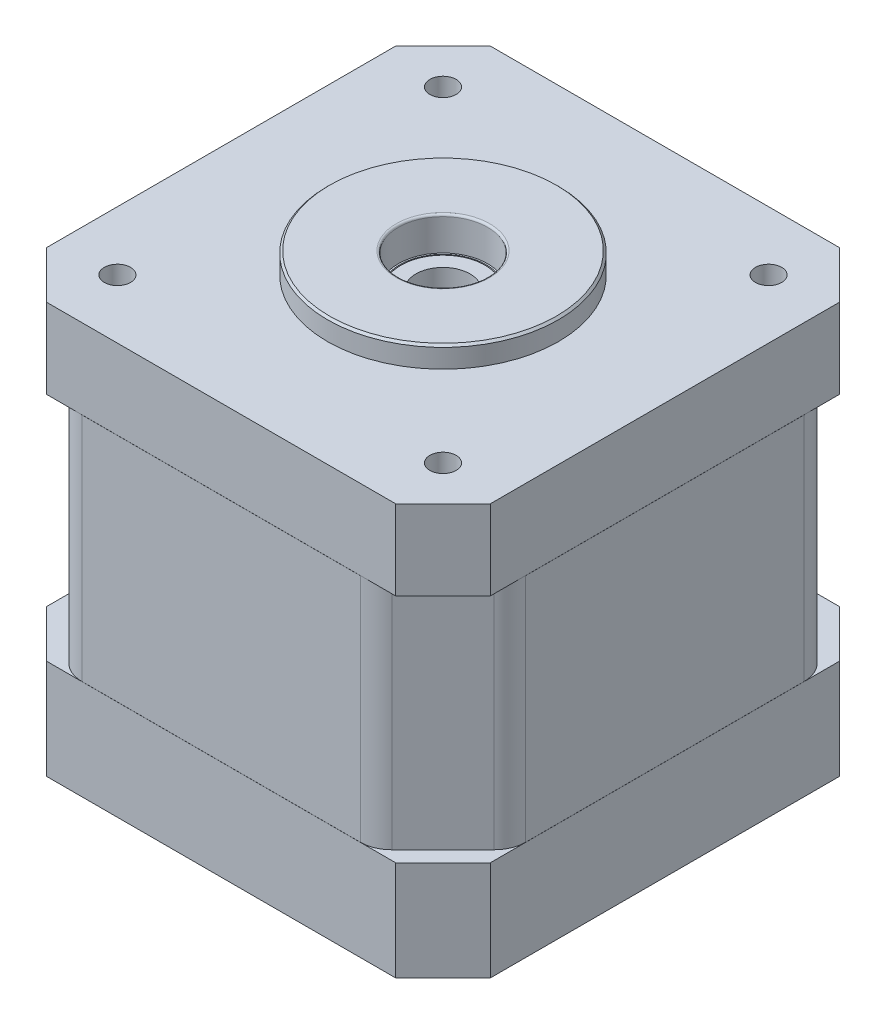
SolidWorks part; units mm, degrees
other "Cámara1"
material "Acero al carbono fundido"
ref_plane "Alzado" through (0, 0, 0) normal (0, 0, 1) x (1, 0, 0)
ref_plane "Planta" through (0, 0, 0) normal (0, 1, 0) x (1, 0, 0)
ref_plane "Vista lateral" through (0, 0, 0) normal (1, 0, 0) x (0, 0, -1)
sketch "Croquis1" plane through (0, 0, 0) normal (0, 1, 0) x (1, 0, 0)
  line L0 (-21.125, 16.625) -> (-16.625, 21.125)
  line L1 (-16.625, -21.125) -> (16.625, -21.125)
  line L2 (-21.125, -16.625) -> (-21.125, 16.625)
  line L3 (-16.625, 21.125) -> (16.625, 21.125)
  line L4 (21.125, -16.625) -> (21.125, 16.625)
  line L5 (-21.125, -21.125) -> (21.125, 21.125) construction
  line L6 (-21.125, 21.125) -> (21.125, -21.125) construction
  line L7 (16.625, 21.125) -> (21.125, 16.625)
  line L8 (-21.125, -16.625) -> (-16.625, -21.125)
  line L9 (16.625, -21.125) -> (21.125, -16.625)
  circle A0 centre (-15.5, 15.5) radius 1
  circle A1 centre (15.5, 15.5) radius 1
  circle A2 centre (-15.5, -15.5) radius 1
  circle A3 centre (15.5, -15.5) radius 1
  point P0 (0, 0)
  dimension "D3" = 2
  dimension "D4" = 31
  dimension "D5" = 31
  dimension "D1" = 42.25
  dimension "D2" = 42.25
extrude "Saliente-Extruir1" add sketch "Croquis1" along normal blind 7.6
sketch "Croquis2" plane through (0, 7.6, 0) normal (0, 1, 0) x (1, 0, 0)
  circle A0 centre (0, 0) radius 11
  dimension "D1" = 22
extrude "Saliente-Extruir2" add sketch "Croquis2" along normal blind 2
chamfer "Chaflán1" distance 0.2 angle 45 1 edges at (0, 9.6, 11)
sketch "Croquis3" plane through (0, 9.6, 0) normal (0, 1, 0) x (1, 0, 0)
  circle A0 centre (0, 0) radius 4.25
  dimension "D1" = 8.5
extrude "Cortar-Extruir1" cut sketch "Croquis3" against normal blind 3.2
fillet "Redondeo1" radius 0.2 1 edges at (0, 9.6, 4.25)
sketch "Croquis4" plane through (0, 6.4, 0) normal (0, 1, 0) x (1, 0, 0)
  circle A0 centre (0, 0) radius 4.1
  circle A1 centre (0, 0) radius 4
  dimension "D1" = 8.2
  dimension "D2" = 8
extrude "Cortar-Extruir2" cut sketch "Croquis4" against normal blind 0.5
sketch "Croquis5" plane through (0, 6.4, 0) normal (0, 1, 0) x (1, 0, 0)
  circle A0 centre (0, 0) radius 2.5
  dimension "D1" = 5
extrude "Saliente-Extruir3" add sketch "Croquis5" along normal blind 21.2
chamfer "Chaflán2" distance 0.3 angle 45 1 edges at (0, 27.6, 2.5)
sketch "Croquis7" plane through (0, 27.6, 0) normal (0, 1, 0) x (1, 0, 0)
  line L0 (0, -2.5) -> (0, 2) construction
  line L1 (-1.5, 2) -> (1.5, 2)
  circle A0 centre (0, 0) radius 2.5 construction
  circle A1 centre (0, 0) radius 2.5 construction
  arc A2 (1.5, 2) -> (-1.5, 2) centre (0, 0) ccw
  point P11 (0, 2)
  dimension "D1" = 4.5
extrude "Cortar-Extruir4" cut sketch "Croquis7" against normal blind 17.2
fillet "Redondeo2" radius 0.1 1 edges at (0, 10.4, -2)
chamfer "Chaflán3" distance 0.3 angle 45 1 edges at (0, 27.6, -2)
sketch "Croquis8" plane through (0, 0, 0) normal (0, -1, 0) x (1, 0, 0)
  line L0 (-14.5, 21.125) -> (14.5, 21.125)
  line L1 (-16.625, 21.125) -> (16.625, 21.125) construction
  line L2 (0, 21.125) -> (0, 0) construction
  line L3 (0, 0) -> (-21.125, 0) construction
  line L4 (-21.125, -16.625) -> (-21.125, 16.625) construction
  line L5 (-21.125, -14.5) -> (-21.125, 14.5)
  line L6 (-21.125, 14.5) -> (-14.5, 21.125)
  line L7 (21.125, -14.5) -> (21.125, 14.5)
  line L8 (-14.5, -21.125) -> (14.5, -21.125)
  line L9 (-21.125, -14.5) -> (-14.5, -21.125)
  line L10 (14.5, -21.125) -> (21.125, -14.5)
  line L11 (21.125, 14.5) -> (14.5, 21.125)
  point P5 (0, 21.125)
  point P14 (-21.125, 0)
  dimension "D1" = 29
  dimension "D2" = 29
extrude "Saliente-Extruir4" add sketch "Croquis8" along normal blind 22
sketch "Croquis9" plane through (0, -22, 0) normal (0, -1, 0) x (1, 0, 0)
  line L8 (16.625, 21.125) -> (-16.625, 21.125)
  line L9 (21.125, 16.625) -> (16.625, 21.125)
  line L10 (21.125, -16.625) -> (21.125, 16.625)
  line L11 (16.625, -21.125) -> (21.125, -16.625)
  line L12 (-16.625, -21.125) -> (16.625, -21.125)
  line L13 (-21.125, -16.625) -> (-16.625, -21.125)
  line L14 (-21.125, 16.625) -> (-21.125, -16.625)
  line L15 (-16.625, 21.125) -> (-21.125, 16.625)
  line L16 (16.625, 21.125) -> (-16.625, 21.125)
  line L17 (21.125, 16.625) -> (16.625, 21.125)
  line L18 (21.125, -16.625) -> (21.125, 16.625)
  line L19 (16.625, -21.125) -> (21.125, -16.625)
  line L20 (-16.625, -21.125) -> (16.625, -21.125)
  line L21 (-21.125, -16.625) -> (-16.625, -21.125)
  line L22 (-21.125, 16.625) -> (-21.125, -16.625)
  line L23 (-16.625, 21.125) -> (-21.125, 16.625)
  dimension "D5" = 0
extrude "Saliente-Extruir5" add sketch "Croquis9" along normal blind 9.5
sketch "Croquis10" plane through (0, -31.5, 0) normal (0, -1, 0) x (1, 0, 0)
  line L0 (-8.175, -21.125) -> (8.175, -21.125)
  line L1 (-16.625, -21.125) -> (16.625, -21.125) construction
  line L2 (0, 0) -> (0, -21.125) construction
  line L3 (8.175, -21.125) -> (8.175, -25.125)
  line L4 (8.175, -25.125) -> (-8.175, -25.125)
  line L5 (-8.175, -25.125) -> (-8.175, -21.125)
  point P5 (0, -21.125)
  dimension "D1" = 16.35
  dimension "D2" = 4
extrude "Saliente-Extruir6" add sketch "Croquis10" against normal blind 3.3
sketch "Croquis11" plane through (0, 6.4, 0) normal (0, 1, 0) x (1, 0, 0)
  circle A0 centre (0, 0) radius 2.575
  circle A1 centre (0, 0) radius 2.5 construction
  circle A2 centre (0, 0) radius 2.5
  arc A3 (-1.5, 2) -> (1.5, 2) centre (0, 0) ccw construction
  dimension "D1" = 5.15
extrude "Cortar-Extruir5" cut sketch "Croquis11" against normal up to surface (0.5 mm away) up to face at (0, 5.9, 4)
sketch "Croquis12" plane through (0, -28.2, 0) normal (0, 1, 0) x (1, 0, 0)
  line L0 (-7, 21.125) -> (7, 21.125)
  line L1 (16.625, 21.125) -> (-16.625, 21.125) construction
  line L2 (-7, 21.125) -> (-7, 25.825)
  line L3 (-7, 25.825) -> (7, 25.825)
  line L4 (7, 25.825) -> (7, 21.125)
  point P5 (0, 21.125)
  dimension "D1" = 14
  dimension "D2" = 4.7
extrude "Saliente-Extruir7" add sketch "Croquis12" along normal blind 1
sketch "Croquis13" plane through (0, -27.2, 0) normal (0, 1, 0) x (1, 0, 0)
  line L0 (16.625, 21.125) -> (-16.625, 21.125) construction
  line L1 (-7.6, 21.125) -> (7.6, 21.125)
  line L2 (7.6, 21.125) -> (7.6, 27.625)
  line L3 (7.6, 27.625) -> (-7.6, 27.625)
  line L4 (-7.6, 27.625) -> (-7.6, 21.125)
  point P0 (0, 21.125)
  point P6 (0, 21.125)
  dimension "D1" = 15.2
  dimension "D2" = 6.5
extrude "Saliente-Extruir8" add sketch "Croquis13" along normal blind 5.5
sketch "Croquis14" plane through (0, 0, -27.625) normal (0, 0, -1) x (-1, 0, 0)
  line L4 (0, -22.7) -> (0, -21.7) construction
  line L5 (7.6, -21.7) -> (-7.6, -21.7) construction
  line L6 (4, -22.7) -> (4, -21.7)
  line L7 (-4, -22.7) -> (-4, -21.7)
  line L8 (-6.6, -26.2) -> (6.6, -26.2)
  line L9 (6.6, -26.2) -> (6.6, -22.7)
  line L10 (6.6, -22.7) -> (-6.6, -22.7)
  line L11 (-6.6, -22.7) -> (-6.6, -26.2)
  line L12 (-6.6, -26.2) -> (6.6, -26.2)
  line L13 (6.6, -26.2) -> (6.6, -22.7)
  line L14 (6.6, -22.7) -> (4, -22.7)
  line L15 (-6.6, -22.7) -> (-6.6, -26.2)
  line L16 (-7.6, -21.7) -> (7.6, -21.7) construction
  line L20 (-4, -21.7) -> (4, -21.7)
  line L21 (-4, -22.7) -> (-6.6, -22.7)
  point P1 (0, -22.7)
  dimension "D2" = 4
  dimension "D1" = 1
  dimension "D3" = 4
extrude "Cortar-Extruir6" cut sketch "Croquis14" against normal blind 4.1
sketch "Croquis15" plane through (0, 0, -23.525) normal (0, 0, -1) x (-1, 0, 0)
  line L0 (-6.6, -24.45) -> (6.6, -24.45) construction
  line L1 (-6.6, -22.7) -> (-6.6, -26.2) construction
  line L2 (6.6, -26.2) -> (6.6, -22.7) construction
  line L3 (-3.0743, -24.2) -> (-2.5743, -24.2)
  line L4 (-4.9643, -24.7) -> (-4.4643, -24.7)
  line L5 (-4.9643, -24.7) -> (-4.9643, -24.2)
  line L6 (-4.9643, -24.2) -> (-4.4643, -24.2)
  line L7 (-4.4643, -24.7) -> (-4.4643, -24.2)
  line L8 (-4.9643, -24.7) -> (-4.4643, -24.2) construction
  line L9 (-4.9643, -24.2) -> (-4.4643, -24.7) construction
  line L10 (-2.5743, -24.7) -> (-2.5743, -24.2)
  line L11 (-3.0743, -24.7) -> (-2.5743, -24.7)
  line L12 (-3.0743, -24.7) -> (-3.0743, -24.2)
  line L13 (-1.1843, -24.2) -> (-0.6843, -24.2)
  line L14 (-0.6843, -24.7) -> (-0.6843, -24.2)
  line L15 (-1.1843, -24.7) -> (-0.6843, -24.7)
  line L16 (-1.1843, -24.7) -> (-1.1843, -24.2)
  line L17 (0.7057, -24.2) -> (1.2057, -24.2)
  line L18 (1.2057, -24.7) -> (1.2057, -24.2)
  line L19 (0.7057, -24.7) -> (1.2057, -24.7)
  line L20 (0.7057, -24.7) -> (0.7057, -24.2)
  line L21 (2.5957, -24.2) -> (3.0957, -24.2)
  line L22 (3.0957, -24.7) -> (3.0957, -24.2)
  line L23 (2.5957, -24.7) -> (3.0957, -24.7)
  line L24 (2.5957, -24.7) -> (2.5957, -24.2)
  line L25 (4.4857, -24.2) -> (4.9857, -24.2)
  line L26 (4.9857, -24.7) -> (4.9857, -24.2)
  line L27 (4.4857, -24.7) -> (4.9857, -24.7)
  line L28 (4.4857, -24.7) -> (4.4857, -24.2)
  point P6 (-4.7143, -24.45)
  dimension "D1" = 0.5
  dimension "D2" = 13.2
  dimension "D3" = 1.8857
  dimension "D4" = 6
extrude "Saliente-Extruir9" add sketch "Croquis15" along normal blind 3.5
chamfer "Chaflán4" distance 0.25 angle 45 24 edges at (-2.8457, -24.7, -27.025) (-2.5957, -24.45, -27.025) (-2.8457, -24.2, -27.025) (-3.0957, -24.45, -27.025) (-4.7357, -24.7, -27.025) (-4.4857, -24.45, -27.025) (-4.7357, -24.2, -27.025) (-4.9857, -24.45, -27.025) (2.8243, -24.7, -27.025) (3.0743, -24.45, -27.025) (2.8243, -24.2, -27.025) (2.5743, -24.45, -27.025) (0.9343, -24.7, -27.025) (1.1843, -24.45, -27.025) (0.9343, -24.2, -27.025) (0.6843, -24.45, -27.025) (-0.9557, -24.7, -27.025) (-0.7057, -24.45, -27.025) (-0.9557, -24.2, -27.025) (-1.2057, -24.45, -27.025) (4.7143, -24.7, -27.025) (4.9643, -24.45, -27.025) (4.7143, -24.2, -27.025) (4.4643, -24.45, -27.025)
sketch "Croquis16" plane through (0, -31.5, 0) normal (0, -1, 0) x (1, 0, 0)
  circle A0 centre (-15.5, 15.5) radius 3
  circle A1 centre (15.5, 15.5) radius 1
  circle A2 centre (15.5, 15.5) radius 1 construction
  circle A3 centre (-15.5, 15.5) radius 1
  circle A4 centre (-15.5, 15.5) radius 1 construction
  circle A5 centre (15.5, -15.5) radius 1
  circle A6 centre (15.5, -15.5) radius 1 construction
  circle A7 centre (-15.5, -15.5) radius 1
  circle A8 centre (-15.5, -15.5) radius 1 construction
  circle A9 centre (15.5, 15.5) radius 3
  circle A10 centre (-15.5, -15.5) radius 3
  circle A11 centre (15.5, -15.5) radius 3
  dimension "D6" = 6
  dimension "D1" = 0
  dimension "D2" = 0
  dimension "D3" = 0
  dimension "D4" = 0
extrude "Cortar-Extruir7" cut sketch "Croquis16" against normal blind 2.5
sketch "Croquis17" plane through (0, -29, 0) normal (0, -1, 0) x (1, 0, 0)
  circle A0 centre (15.5, 15.5) radius 2.75
  circle A1 centre (-15.5, 15.5) radius 2.75
  circle A2 centre (15.5, -15.5) radius 2.75
  circle A3 centre (-15.5, -15.5) radius 2.75
  dimension "D1" = 5.5
  dimension "D2" = 5.5
  dimension "D3" = 5.5
  dimension "D4" = 5.5
extrude "Saliente-Extruir10" add sketch "Croquis17" along normal blind 2.3
fillet "Redondeo3" radius 0.6 4 edges at (15.5, -31.3, -18.25) (-15.5, -31.3, -18.25) (-15.5, -31.3, 12.75) (15.5, -31.3, 12.75)
sketch "Croquis18" plane through (0, -31.3, 0) normal (0, -1, 0) x (1, 0, 0)
  line L0 (16.8789, 14.1211) -> (14.1211, 16.8789) construction
  line L1 (15.5, 15.5) -> (15.5, 17.65) construction
  line L2 (17.3031, 14.5454) -> (16.3485, 15.5)
  line L3 (16.4546, 13.6969) -> (15.5, 14.6515)
  line L4 (14.1211, 14.1211) -> (16.8789, 16.8789) construction
  line L5 (14.5454, 13.6969) -> (15.5, 14.6515)
  line L6 (13.6969, 14.5454) -> (14.6515, 15.5)
  line L7 (16.4546, 17.3031) -> (17.3031, 16.4546)
  line L8 (17.3031, 14.5454) -> (16.4546, 13.6969)
  line L9 (14.5454, 13.6969) -> (13.6969, 14.5454)
  line L10 (13.6969, 16.4546) -> (14.5454, 17.3031)
  line L11 (15.5, 16.3485) -> (14.5454, 17.3031)
  line L12 (16.3485, 15.5) -> (17.3031, 16.4546)
  line L13 (17.3031, 14.5454) -> (14.5454, 17.3031) construction
  line L14 (14.6515, 15.5) -> (13.6969, 16.4546)
  line L15 (14.5454, 13.6969) -> (17.3031, 16.4546) construction
  line L16 (15.5, 16.3485) -> (16.4546, 17.3031)
  line L17 (16.4546, 13.6969) -> (13.6969, 16.4546) construction
  line L18 (-17.3031, 16.4546) -> (-16.4546, 17.3031)
  line L19 (13.6969, 14.5454) -> (16.4546, 17.3031) construction
  line L20 (-15.5, 16.3485) -> (-14.5454, 17.3031)
  line L21 (-14.5454, 13.6969) -> (-15.5, 14.6515)
  line L22 (-16.3485, 15.5) -> (-17.3031, 16.4546)
  line L23 (-13.6969, 14.5454) -> (-14.5454, 13.6969)
  line L24 (-16.4546, 13.6969) -> (-15.5, 14.6515)
  line L25 (-14.5454, 17.3031) -> (-13.6969, 16.4546)
  line L26 (-15.5, 15.5) -> (-15.5, 17.65) construction
  line L27 (-15.5, 16.3485) -> (-16.4546, 17.3031)
  line L28 (-13.6969, 14.5454) -> (-14.6515, 15.5)
  line L29 (-16.4546, 13.6969) -> (-17.3031, 14.5454)
  line L30 (-17.3031, 14.5454) -> (-16.3485, 15.5)
  line L31 (-16.8789, 14.1211) -> (-14.1211, 16.8789) construction
  line L32 (-14.6515, 15.5) -> (-13.6969, 16.4546)
  line L33 (-14.1211, 14.1211) -> (-16.8789, 16.8789) construction
  line L34 (-13.6969, -16.4546) -> (-14.6515, -15.5)
  line L35 (-14.6515, -15.5) -> (-13.6969, -14.5454)
  line L36 (-15.5, -14.6515) -> (-16.4546, -13.6969)
  line L37 (-14.5454, -17.3031) -> (-15.5, -16.3485)
  line L38 (-17.3031, -16.4546) -> (-16.3485, -15.5)
  line L39 (-13.6969, -16.4546) -> (-14.5454, -17.3031)
  line L40 (-15.5, -14.6515) -> (-14.5454, -13.6969)
  line L41 (-16.4546, -17.3031) -> (-15.5, -16.3485)
  line L42 (-16.3485, -15.5) -> (-17.3031, -14.5454)
  line L43 (-16.4546, -17.3031) -> (-17.3031, -16.4546)
  line L44 (-14.1211, -16.8789) -> (-16.8789, -14.1211) construction
  line L45 (-14.5454, -13.6969) -> (-13.6969, -14.5454)
  line L46 (-16.8789, -16.8789) -> (-14.1211, -14.1211) construction
  line L47 (-15.5, -15.5) -> (-15.5, -13.35) construction
  line L48 (-17.3031, -14.5454) -> (-16.4546, -13.6969)
  line L49 (16.3485, -15.5) -> (17.3031, -14.5454)
  line L50 (13.6969, -16.4546) -> (14.6515, -15.5)
  line L51 (16.8789, -16.8789) -> (14.1211, -14.1211) construction
  line L52 (17.3031, -16.4546) -> (16.4546, -17.3031)
  line L53 (14.6515, -15.5) -> (13.6969, -14.5454)
  line L54 (14.5454, -17.3031) -> (15.5, -16.3485)
  line L55 (14.1211, -16.8789) -> (16.8789, -14.1211) construction
  line L56 (15.5, -15.5) -> (15.5, -13.35) construction
  line L57 (14.5454, -17.3031) -> (13.6969, -16.4546)
  line L58 (16.4546, -13.6969) -> (17.3031, -14.5454)
  line L59 (17.3031, -16.4546) -> (16.3485, -15.5)
  line L60 (16.4546, -17.3031) -> (15.5, -16.3485)
  line L61 (15.5, -14.6515) -> (16.4546, -13.6969)
  line L62 (13.6969, -14.5454) -> (14.5454, -13.6969)
  line L63 (15.5, -14.6515) -> (14.5454, -13.6969)
  circle A0 centre (15.5, 15.5) radius 2.15 construction
  point P4 (15.5, 15.5)
  point P8 (15.5, 15.5)
  point P16 (15.5, 15.5)
  point P28 (-15.5, 15.5)
  point P30 (-15.5, 15.5)
  point P37 (-15.5, 15.5)
  point P49 (-15.5, -15.5)
  point P51 (-15.5, -15.5)
  point P58 (-15.5, -15.5)
  point P70 (15.5, -15.5)
  point P72 (15.5, -15.5)
  point P79 (15.5, -15.5)
  dimension "D1" = 3.9
  dimension "D2" = 45
  dimension "D5" = 3.9
  dimension "D6" = 45
  dimension "D9" = 45
  dimension "D8" = 3.9
  dimension "D10" = 3.9
  dimension "D11" = 45
  dimension "D12" = 3.9
  dimension "D13" = 45
  dimension "D14" = 3.9
  dimension "D15" = 45
  dimension "D3" = 0.6
  dimension "D4" = 0.6
  dimension "D7" = 0.6
extrude "Cortar-Extruir8" cut sketch "Croquis18" against normal blind 1.1 draft 10
fillet "Redondeo4" radius 0.2 48 edges at (-17.166, -30.75, -14.5454) (-16.2114, -30.75, -15.5) (-17.166, -30.75, -16.4546) (-16.4546, -30.75, -17.166) (-15.5, -30.75, -16.2114) (-14.5454, -30.75, -17.166) (-13.834, -30.75, -16.4546) (-14.7886, -30.75, -15.5) (-13.834, -30.75, -14.5454) (-14.5454, -30.75, -13.834) (-15.5, -30.75, -14.7886) (-16.4546, -30.75, -13.834) (13.834, -30.75, -14.5454) (14.7886, -30.75, -15.5) (13.834, -30.75, -16.4546) (14.5454, -30.75, -17.166) (15.5, -30.75, -16.2114) (16.4546, -30.75, -17.166) (17.166, -30.75, -16.4546) (16.2114, -30.75, -15.5) (17.166, -30.75, -14.5454) (16.4546, -30.75, -13.834) (15.5, -30.75, -14.7886) (14.5454, -30.75, -13.834) (14.7886, -30.75, 15.5) (13.834, -30.75, 14.5454) (14.5454, -30.75, 13.834) (15.5, -30.75, 14.7886) (16.4546, -30.75, 13.834) (17.166, -30.75, 14.5454) (16.2114, -30.75, 15.5) (17.166, -30.75, 16.4546) (16.4546, -30.75, 17.166) (15.5, -30.75, 16.2114) (14.5454, -30.75, 17.166) (13.834, -30.75, 16.4546) (-15.5, -30.75, 14.7886) (-14.7886, -30.75, 15.5) (-15.5, -30.75, 16.2114) (-16.2114, -30.75, 15.5) (-17.166, -30.75, 14.5454) (-16.4546, -30.75, 13.834) (-14.5454, -30.75, 13.834) (-13.834, -30.75, 14.5454) (-13.834, -30.75, 16.4546) (-14.5454, -30.75, 17.166) (-17.166, -30.75, 16.4546) (-16.4546, -30.75, 17.166)
sketch "Croquis19" plane through (0, -31.5, 0) normal (0, -1, 0) x (1, 0, 0)
  circle A0 centre (0, 0) radius 4.55
  dimension "D1" = 9.1
extrude "Cortar-Extruir9" cut sketch "Croquis19" against normal blind 3.7
sketch "Croquis20" plane through (0, -27.8, 0) normal (0, -1, 0) x (1, 0, 0)
  circle A2 centre (0, 0) radius 5.15
  circle A3 centre (0, 0) radius 5.15
  dimension "D1" = 0.6
extrude "Cortar-Extruir10" cut sketch "Croquis20" along normal blind 2.5
fillet "Redondeo5" radius 3 8 edges
sketch "Croquis24" plane through (0, -22, 0) normal (0, 1, 0) x (1, 0, 0)
  line L8 (14.5, 21.125) -> (-14.5, 21.125)
  line L9 (21.125, 14.5) -> (14.5, 21.125)
  line L10 (21.125, -14.5) -> (21.125, 14.5)
  line L11 (14.5, -21.125) -> (21.125, -14.5)
  line L12 (-14.5, -21.125) -> (14.5, -21.125)
  line L13 (-21.125, -14.5) -> (-14.5, -21.125)
  line L14 (-21.125, 14.5) -> (-21.125, -14.5)
  line L15 (-14.5, 21.125) -> (-21.125, 14.5)
  line L16 (14.5, 21.125) -> (-14.5, 21.125)
  line L17 (21.125, 14.5) -> (14.5, 21.125)
  line L18 (21.125, -14.5) -> (21.125, 14.5)
  line L19 (14.5, -21.125) -> (21.125, -14.5)
  line L20 (-14.5, -21.125) -> (14.5, -21.125)
  line L21 (-21.125, -14.5) -> (-14.5, -21.125)
  line L22 (-21.125, 14.5) -> (-21.125, -14.5)
  line L23 (-14.5, 21.125) -> (-21.125, 14.5)
  dimension "D1" = 0
extrude "Cortar-Extruir-Lámina1" cut sketch "Croquis24" along normal blind 0.01 thin thin type one direction reverse wall 2
sketch "Croquis25" plane through (0, 0, 0) normal (0, -1, 0) x (1, 0, 0)
  line L8 (-14.5, -21.125) -> (14.5, -21.125)
  line L9 (-21.125, -14.5) -> (-14.5, -21.125)
  line L10 (-21.125, 14.5) -> (-21.125, -14.5)
  line L11 (-14.5, 21.125) -> (-21.125, 14.5)
  line L12 (14.5, 21.125) -> (-14.5, 21.125)
  line L13 (21.125, 14.5) -> (14.5, 21.125)
  line L14 (21.125, -14.5) -> (21.125, 14.5)
  line L15 (14.5, -21.125) -> (21.125, -14.5)
  line L16 (-14.5, -21.125) -> (14.5, -21.125)
  line L17 (-21.125, -14.5) -> (-14.5, -21.125)
  line L18 (-21.125, 14.5) -> (-21.125, -14.5)
  line L19 (-14.5, 21.125) -> (-21.125, 14.5)
  line L20 (14.5, 21.125) -> (-14.5, 21.125)
  line L21 (21.125, 14.5) -> (14.5, 21.125)
  line L22 (21.125, -14.5) -> (21.125, 14.5)
  line L23 (14.5, -21.125) -> (21.125, -14.5)
  dimension "D1" = 0
extrude "Cortar-Extruir-Lámina2" cut sketch "Croquis25" along normal blind 0.01 thin thin type one direction reverse wall 2
pattern_linear "MatrizL1" [suppressed] count 60 spacing 0.5 of bodies 124
hole_wizard "M3 Tapped Hole1" positions "Sketch2" profile "Sketch1" tap size "M3" standard "ISO"
sketch "Sketch2" plane through (0, 7.6, 0) normal (0, 1, 0) x (1, 0, 0)
  point P1 (-15.5, 15.5)
  point P4 (15.5, 15.5)
  point P7 (15.5, -15.5)
  point P10 (-15.5, -15.5)
sketch "Sketch1" plane through (-15.5, 7.6, -15.5) normal (1, 0, 0) x (0, 0, 1)
  line L0 (0, 0) -> (0, 8.2511)
  line L1 (0, 8.2511) -> (1.25, 7.5)
  line L2 (1.25, 7.5) -> (1.25, 0)
  line L5 (1.25, 0) -> (0, 0)
  line L10 (0, 8.2511) -> (-1.25, 7.5) construction
  line L11 (0, -6.35) -> (0, 107.95) construction
  dimension "Tap Drill Dia." = 2.5
  dimension "Tap Drill Depth" = 7.5
  dimension "Drill Angle" = 118
cosmetic thread "Hole Thread1" parameters "D1"=6, "D2"=3
cosmetic thread "Hole Thread2" parameters "D1"=6, "D2"=3
cosmetic thread "Hole Thread3" parameters "D1"=6, "D2"=3
cosmetic thread "Hole Thread4" parameters "D1"=6, "D2"=3
sketch "草图1" plane through (0, 27.6, 0) normal (0, 1, 0) x (1, 0, 0)
  circle A2 centre (0, 0) radius 2.575 construction
  circle A3 centre (0, 0) radius 2.575
extrude "切除-拉伸1" cut sketch "草图1" against normal blind 30
